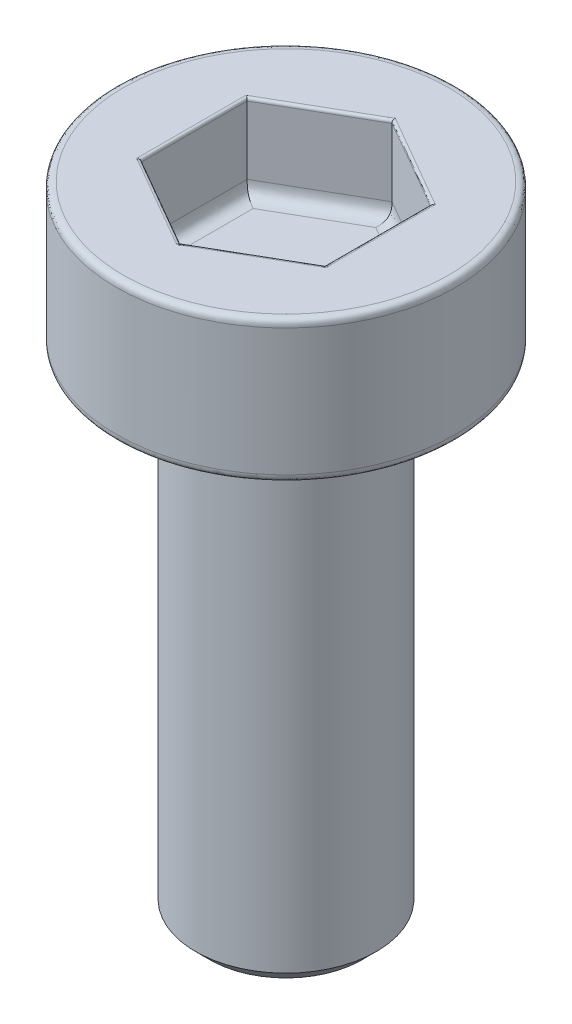
SolidWorks part; units mm, degrees
ref_plane "Front Plane" through (0, 0, 0) normal (0, 0, 1) x (1, 0, 0)
ref_plane "Top Plane" through (0, 0, 0) normal (0, 1, 0) x (1, 0, 0)
ref_plane "Right Plane" through (0, 0, 0) normal (1, 0, 0) x (0, 0, -1)
sketch "Sketch2" plane through (0, 0, 0) normal (1, 0, 0) x (0, 0, -1)
  line L0 (0, 0) -> (0, 45)
  line L1 (0, 45) -> (12, 45)
  line L2 (12, 45) -> (12, 35)
  line L3 (12, 35) -> (6.4, 35)
  line L4 (6.4, 35) -> (6.4, 0)
  line L5 (6.4, 0) -> (0, 0)
  dimension "D1" = 6.4
  dimension "D2" = 12
  dimension "D3" = 10
  dimension "D4" = 45
revolve "Revolve1" add sketch "Sketch2" angle 360 about L0
chamfer "Chamfer1" distance 1 angle 45 1 edges at (0, 0, -6.4)
sketch "Sketch3" plane through (0, 45, 0) normal (0, 1, 0) x (1, 0, 0)
  line L1 (0, 7.5056) -> (-6.5, 3.7528)
  line L2 (-6.5, 3.7528) -> (-6.5, -3.7528)
  line L3 (-6.5, -3.7528) -> (0, -7.5056)
  line L4 (0, -7.5056) -> (6.5, -3.7528)
  line L5 (6.5, -3.7528) -> (6.5, 3.7528)
  line L6 (6.5, 3.7528) -> (0, 7.5056)
  circle A0 centre (0, 0) radius 6.5 construction
  dimension "D1" = 13
extrude "Cut-Extrude1" cut sketch "Sketch3" against normal blind 6
fillet "Fillet1" radius 1 6 edges at (6.5, 39, 0) (3.25, 39, 5.6292) (-3.25, 39, 5.6292) (-6.5, 39, 0) (-3.25, 39, -5.6292) (3.25, 39, -5.6292) curvature continuous yes
fillet "Fillet2" radius 0.5 2 edges at (0, 35, -12) (0, 45, -12) curvature continuous yes
ref_axis "Axis1" through (0, 36, 0) along (0, -1, 0)
fillet "Fillet3" radius 0.2 6 edges at (-6.5, 45, 0) (-3.25, 45, 5.6292) (3.25, 45, 5.6292) (6.5, 45, 0) (3.25, 45, -5.6292) (-3.25, 45, -5.6292) curvature continuous yes
